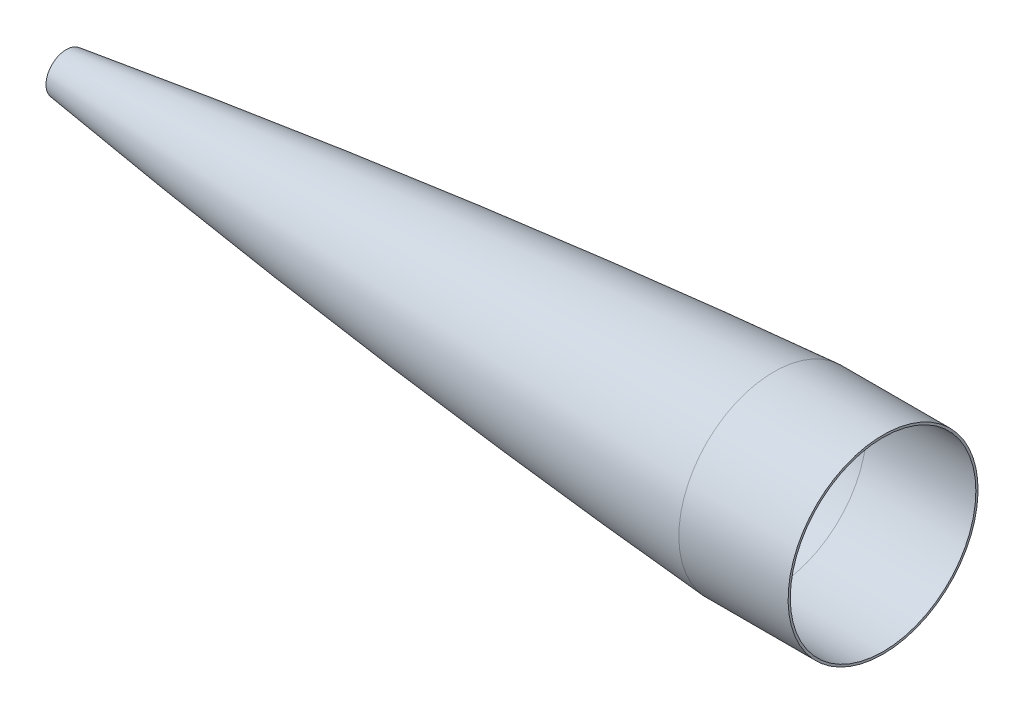
SolidWorks part; units mm, degrees
other "Markup1"
sketch "Sketch19" plane through (863.2353, 87, -87) normal (0.5122, 0.1711, -0.8417) x (-0.8532, -0.0108, -0.5214)
other "Markup2"
sketch "Sketch20" plane through (863.2353, 87, -87) normal (0.5122, 0.1711, -0.8417) x (-0.8532, -0.0108, -0.5214)
material "E-Glass Fiber"
ref_plane "Płaszczyzna przednia" through (0, 0, 0) normal (0, 0, 1) x (1, 0, 0)
ref_plane "Płaszczyzna górna" through (0, 0, 0) normal (0, 1, 0) x (1, 0, 0)
ref_plane "Płaszczyzna prawa" through (0, 0, 0) normal (1, 0, 0) x (0, 0, -1)
ref_plane "Plane1" through (0, 0, 0) normal (0, 0, -1) x (-1, 0, 0)
sketch "Sketch1" plane through (0, 0, 0) normal (0, 0, -1) x (-1, 0, 0)
  line L2 (-763.2353, 0) -> (0, 0) construction
  line L8 (-763.3824, 85) -> (-763.2353, 85)
  line L9 (-763.3824, 87) -> (-763.1616, 87)
  line L10 (0, 0) -> (18.4685, 0)
  line L11 (18.4685, 0) -> (0.2953, 1.9781)
  line L12 (-763.3824, 87) -> (-763.3824, 85)
  arc A0 (0, 0) -> (-763.2353, 85) centre (-1520.6726, -10185.346) ccw
  arc A3 (0.2953, 1.9781) -> (-763.1616, 87) centre (-1520.6726, -10185.346) ccw
  dimension "D1" = 85
  dimension "D2" = 2
revolve "Revolve1" add sketch "Sketch1" angle 360 about L2 reverse direction yes
sketch "Sketch14" plane through (0, 0, 0) normal (0, 0, -1) x (-1, 0, 0)
  line L0 (-763.2353, 85) -> (-763.2353, -85) construction
  line L1 (-763.2353, 0) -> (-863.2353, 0) construction
  line L2 (-863.2353, 0) -> (-863.2353, 85) construction
  line L9 (-763.3824, 87) -> (-763.3824, 85)
  line L10 (-763.3824, 87) -> (-863.2353, 87)
  line L11 (-863.2353, 87) -> (-863.2353, 85)
  line L12 (-763.3824, 85) -> (-863.2353, 85)
  arc A0 (-763.2353, -85) -> (0, 0) centre (-1520.6726, 10185.346) ccw construction
  dimension "D1" = 100
revolve "Revolve4" add sketch "Sketch14" angle 360 about L1
sketch "Sketch15" plane through (0, 0, 0) normal (0, 0, 1) x (1, 0, 0)
  line L0 (-17.7797, -0.075) -> (114.9971, 0)
  line L1 (-18.4685, 0) -> (-0.2953, -1.9781) construction
  line L2 (763.2353, 0) -> (0, 0) construction
  line L3 (114.9971, 0) -> (114.9971, 42.3088)
  line L4 (114.9971, 42.3088) -> (-24.7937, 42.3088)
  line L5 (-24.7937, 42.3088) -> (-24.7937, -36.0986)
  line L6 (-24.7937, -36.0986) -> (114.9971, -36.0986)
  line L7 (114.9971, -36.0986) -> (114.9971, 0)
  line L8 (114.9971, 0) -> (114.9971, -36.0986)
  dimension "D1" = 132.7768
extrude "Cut-Extrude1" cut sketch "Sketch15" along normal mid plane 100 contours L6 L7 L3 L4 L5 region at (45.1017, 3.1051, 0)
